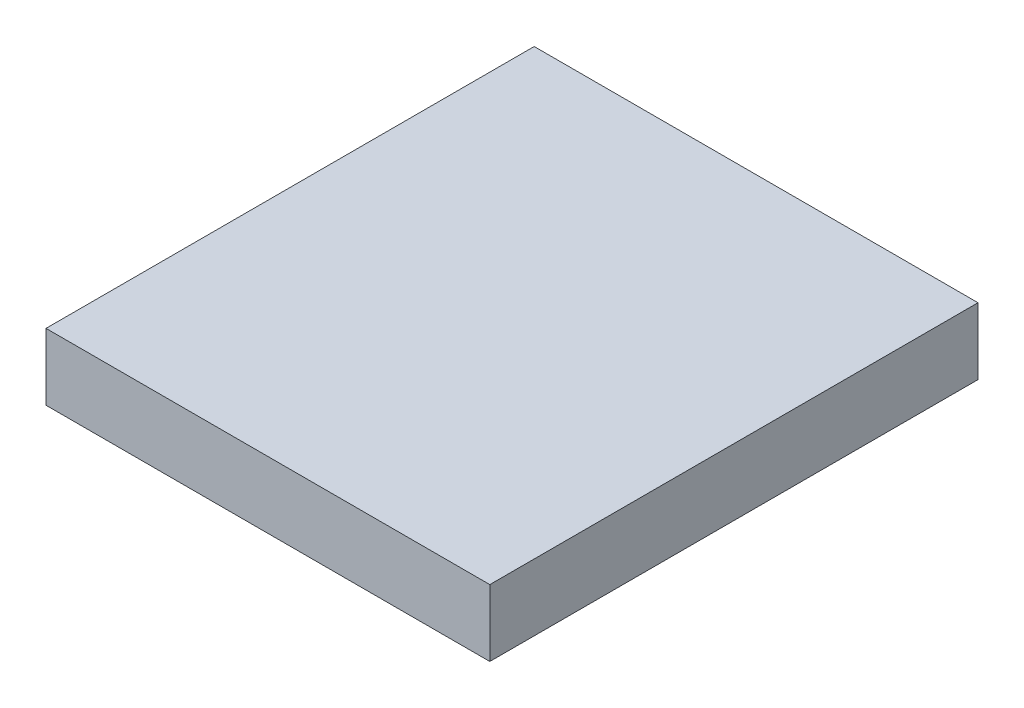
SolidWorks part; units mm, degrees
note: The reader was unsure of these and kept them because the rebuilt part matched: thickness of "Base-Flange1", "Sheet-Metal1".
ref_plane "Front" through (0, 0, 0) normal (0, 0, 1) x (1, 0, 0)
ref_plane "Top" through (0, 0, 0) normal (0, 1, 0) x (1, 0, 0)
ref_plane "Right" through (0, 0, 0) normal (1, 0, 0) x (0, 0, -1)
sketch "Sketch1" plane through (0, 0, 0) normal (0, 1, 0) x (1, 0, 0)
  line L1 (-7.9375, 8.7312) -> (7.9375, 8.7312)
  line L2 (-7.9375, 8.7312) -> (-7.9375, -8.7313)
  line L3 (-7.9375, -8.7313) -> (7.9375, -8.7313)
  line L4 (7.9375, 8.7312) -> (7.9375, -8.7313)
  line L5 (-7.9375, 8.7312) -> (7.9375, -8.7313) construction
  line L6 (-7.9375, -8.7313) -> (7.9375, 8.7312) construction
  point P0 (0, 0)
  dimension "D1" = 15.875
  dimension "D2" = 17.4625
base flange "Base-Flange1" sketch "Sketch1" thickness 2.3825 reverse thickness direction no parameters "D1"=10
sketch "Bend-Lines1" [suppressed] plane through (0, 0, 0) normal (0, 1, 0) x (1, 0, 0)
sketch "Bounding-Box1" [suppressed] plane through (0, 0, 0) normal (0, 1, 0) x (1, 0, 0)
sheet metal parameters "Sheet-Metal1" thickness 2.3825 parameters "D1"=10, "D7"=2.3812
flat pattern "Flat-Pattern1" [suppressed]
sketch "Bend-Lines2" plane through (0, 0, 0) normal (0, 1, 0) x (1, 0, 0)
sketch3d "Bounding-Box2" [suppressed]
  line L0 (-7.9375, 8.7312, 0) -> (-7.9375, -8.7313, 0) construction
  line L1 (7.9375, 8.7312, 0) -> (7.9375, -8.7313, 0) construction
  line L2 (-7.9375, 8.7312, 0) -> (7.9375, 8.7312, 0) construction
  line L3 (-7.9375, -8.7313, 0) -> (7.9375, -8.7313, 0) construction
